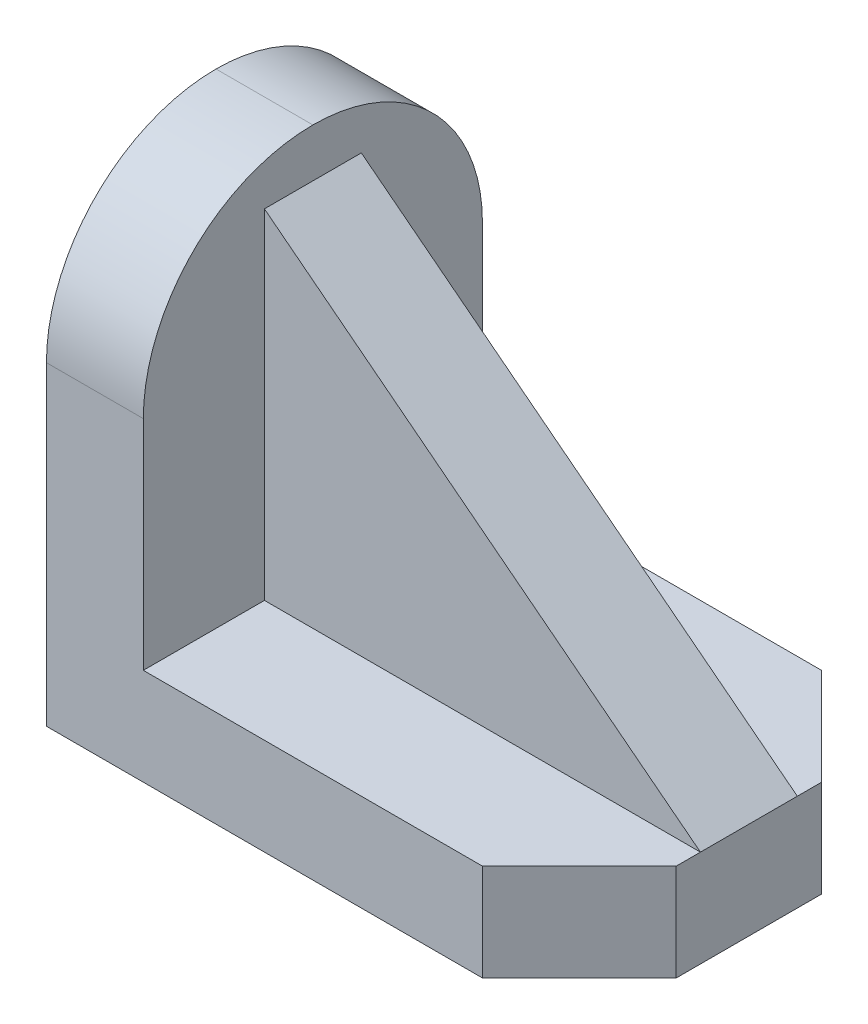
SolidWorks part; units mm, degrees
ref_plane "Front Plane" through (0, 0, 0) normal (0, 0, 1) x (1, 0, 0)
ref_plane "Top Plane" through (0, 0, 0) normal (0, 1, 0) x (1, 0, 0)
ref_plane "Right Plane" through (0, 0, 0) normal (1, 0, 0) x (0, 0, -1)
sketch "Sketch10" plane through (0, 0, 0) normal (0, 1, 0) x (1, 0, 0)
  line L2 (-33000, 21000) -> (33000, 21000)
  line L3 (-33000, 21000) -> (-33000, -21000)
  line L4 (-33000, -21000) -> (33000, -21000)
  line L5 (33000, 21000) -> (33000, -21000)
  line L6 (-33000, 21000) -> (33000, -21000) construction
  line L7 (-33000, -21000) -> (33000, 21000) construction
  point P1 (0, 0)
  dimension "D1" = 66000
  dimension "D2" = 42000
extrude "Boss-Extrude3" add sketch "Sketch10" along normal blind 12000
chamfer "Chamfer1" distance 12000 distance2 12000 2 edges at (33000, 6000, -21000) (33000, 6000, 21000)
sketch "Sketch14" plane through (-33000, 0, 0) normal (-1, 0, 0) x (0, 0, 1)
  line L2 (-21000, 12000) -> (21000, 12000)
  line L3 (-21000, 12000) -> (-21000, 60000)
  line L4 (-21000, 60000) -> (21000, 60000)
  line L5 (21000, 12000) -> (21000, 60000)
  dimension "D1" = 48000
extrude "Boss-Extrude6" add sketch "Sketch14" against normal blind 12000 separate body
fillet "Fillet1" radius 21000 2 edges at (-27000, 60000, 21000) (-27000, 60000, -21000)
sketch "Sketch15" plane through (0, 0, 0) normal (0, 0, 1) x (1, 0, 0)
  line L0 (-21000, 54000) -> (-21000, 12000)
  line L2 (-21000, 12000) -> (33000, 12000)
  line L3 (33000, 12000) -> (-21000, 54000)
  dimension "D1" = 42000
extrude "Boss-Extrude7" add sketch "Sketch15" along normal mid plane 12000
